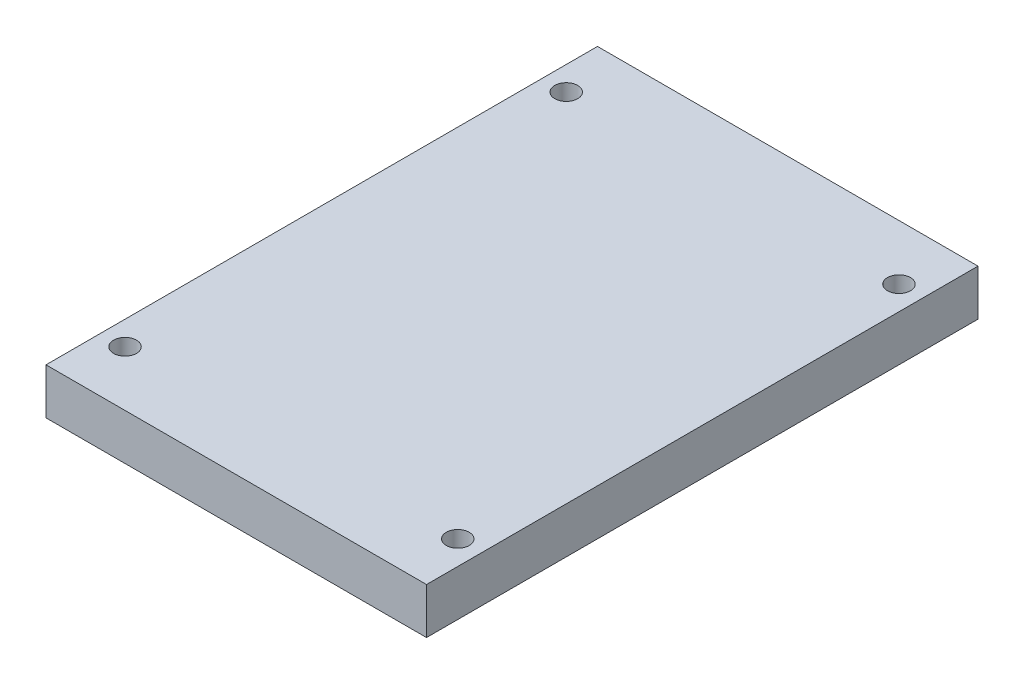
SolidWorks part; units mm, degrees
ref_plane "Front Plane" through (0, 0, 0) normal (0, 0, 1) x (1, 0, 0)
ref_plane "Top Plane" through (0, 0, 0) normal (0, 1, 0) x (1, 0, 0)
ref_plane "Right Plane" through (0, 0, 0) normal (1, 0, 0) x (0, 0, -1)
sketch "Sketch1" plane through (0, 0, 0) normal (0, 1, 0) x (1, 0, 0)
  line L1 (0, 0) -> (-53.594, 0)
  line L2 (0, 0) -> (0, 76.2)
  line L3 (0, 76.2) -> (-53.594, 76.2)
  line L4 (-53.594, 0) -> (-53.594, 76.2)
  dimension "D1" = 76.2
  dimension "D2" = 53.594
extrude "Boss-Extrude1" add sketch "Sketch1" along normal blind 6.35
sketch "Sketch2" plane through (0, 6.35, 0) normal (0, 1, 0) x (1, 0, 0)
  line L0 (0, 0) -> (0, 76.2) construction
  line L1 (-53.594, 0) -> (0, 0) construction
  circle A0 centre (-3.81, 7.62) radius 1.5875
  circle A4 centre (-3.81, 68.58) radius 1.5875
  dimension "D2" = 3.175
  dimension "D1" = 3.81
  dimension "D3" = 7.62
  dimension "D4" = 68.58
extrude "Cut-Extrude1" cut sketch "Sketch2" against normal through all
ref_plane "KORAL!!!" through (-26.797, 0, 0) normal (1, 0, 0) x (0, 0, -1)
mirror "Mirror1" about plane through (-26.797, 0, 0) normal (1, 0, 0) of "Cut-Extrude1"
sketch "Sketch3" plane through (0, 6.35, 0) normal (0, 1, 0) x (1, 0, 0)
  line L0 (0, 0) -> (-0.508, 0)
  line L1 (-53.594, 0) -> (0, 0) construction
  line L2 (-0.508, 0) -> (-0.508, 76.2)
  line L3 (0, 76.2) -> (-53.594, 76.2) construction
  line L4 (-0.508, 76.2) -> (0, 76.2)
  line L5 (0, 76.2) -> (0, 0)
  dimension "D1" = 0.508
extrude "Cut-Extrude2" cut sketch "Sketch3" against normal through all
mirror "Mirror2" about plane through (-26.797, 0, 0) normal (1, 0, 0) of "Cut-Extrude2"
